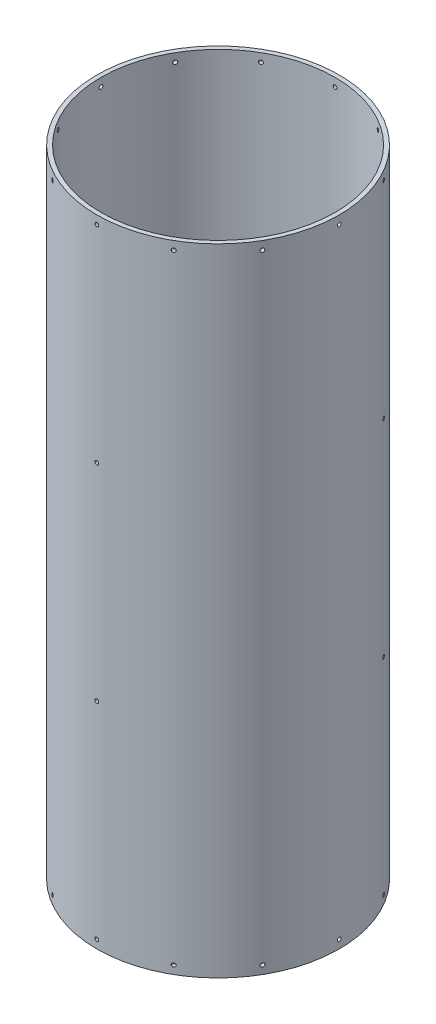
SolidWorks part; units mm, degrees
material "PVC Rigid"
ref_plane "Front Plane" through (0, 0, 0) normal (0, 0, 1) x (1, 0, 0)
ref_plane "Top Plane" through (0, 0, 0) normal (0, 1, 0) x (1, 0, 0)
ref_plane "Right Plane" through (0, 0, 0) normal (1, 0, 0) x (0, 0, -1)
sketch "Sketch1" plane through (0, 0, 0) normal (0, 1, 0) x (1, 0, 0)
  circle A0 centre (0, 0) radius 92.075
  circle A1 centre (0, 0) radius 88.9
  dimension "D1" = 184.15
  dimension "D2" = 177.8
extrude "Boss-Extrude1" add sketch "Sketch1" along normal mid plane 482.854
ref_plane "Plane1" through (0, 0, 92.075) normal (0, 0, 1) x (1, 0, 0)
sketch "Sketch3" plane through (0, 0, 92.075) normal (0, 0, 1) x (1, 0, 0)
  line L0 (0, -55) -> (0, 55) construction
  line L1 (-92.075, -241.427) -> (92.075, -241.427) construction
  circle A0 centre (0, -235.077) radius 1.4351
  dimension "D1" = 2.8702
  dimension "D2" = 6.35
extrude "Cut-Extrude1" cut sketch "Sketch3" against normal blind 19.304
pattern_circular "CirPattern1" count 12 over 360 about axis through (0, 241.427, 0) along (0, -1, 0) of "Cut-Extrude1" reverse direction yes
mirror "Mirror1" about plane through (0, 0, 0) normal (0, 1, 0) of "CirPattern1", "Cut-Extrude1"
sketch "Sketch4" plane through (0, 0, 92.075) normal (0, 0, 1) x (1, 0, 0)
  line L0 (0, -55) -> (0, 55) construction
  circle A0 centre (0, -78.359) radius 1.4351
  circle A1 centre (0, 78.359) radius 1.4351
  circle A2 centre (0, 235.077) radius 1.4351 construction
  circle A3 centre (0, -235.077) radius 1.4351 construction
  dimension "D1" = 2.8702
  dimension "D2" = 2.8702
  dimension "D3" = 156.718
  dimension "D4" = 156.718
extrude "Cut-Extrude2" cut sketch "Sketch4" against normal blind 25.146
pattern_circular "CirPattern2" count 3 over 360 about axis through (0, 241.427, 0) along (0, -1, 0) of "Cut-Extrude2"
